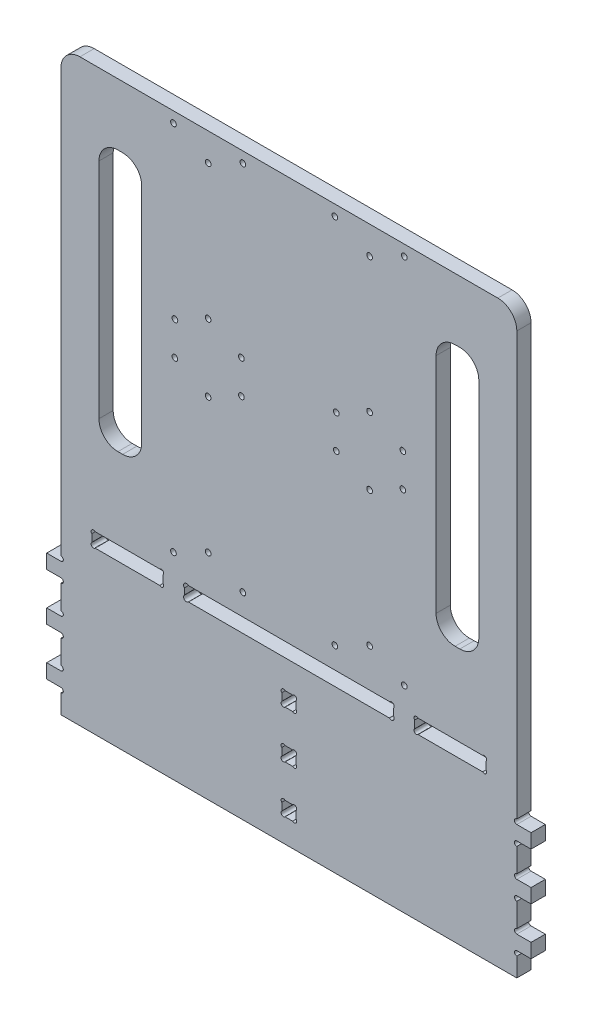
SolidWorks part; units mm, degrees
material "Balsa"
ref_plane "Front Plane" through (0, 0, 0) normal (0, 0, 1) x (1, 0, 0)
ref_plane "Top Plane" through (0, 0, 0) normal (0, 1, 0) x (1, 0, 0)
ref_plane "Right Plane" through (0, 0, 0) normal (1, 0, 0) x (0, 0, -1)
sketch "Sketch1" plane through (0, 0, 0) normal (0, 0, 1) x (1, 0, 0)
  line L0 (0, 222.25) -> (0, 0) construction
  line L1 (-304.8, 0) -> (304.8, 0)
  line L2 (-304.8, 0) -> (-304.8, 222.25)
  line L3 (-304.8, 222.25) -> (304.8, 222.25)
  line L4 (304.8, 0) -> (304.8, 222.25)
  line L5 (-304.8, 222.25) -> (-304.8, 184.15) construction
  line L6 (-304.8, 184.15) -> (-323.85, 184.15)
  line L7 (-304.8, 184.15) -> (-304.8, 165.1)
  line L8 (-304.8, 165.1) -> (-323.85, 165.1)
  line L9 (-323.85, 184.15) -> (-323.85, 165.1)
  line L10 (-304.8, 57.15) -> (-323.85, 57.15)
  line L11 (-304.8, 57.15) -> (-304.8, 38.1)
  line L12 (-304.8, 38.1) -> (-323.85, 38.1)
  line L13 (-323.85, 57.15) -> (-323.85, 38.1)
  line L14 (-304.8, 120.65) -> (-323.85, 120.65)
  line L15 (-304.8, 120.65) -> (-304.8, 101.6)
  line L16 (-304.8, 101.6) -> (-323.85, 101.6)
  line L17 (-323.85, 120.65) -> (-323.85, 101.6)
  line L18 (-323.85, 184.15) -> (-323.85, 222.25) construction
  line L19 (-323.85, 0) -> (-323.85, 38.1) construction
  line L20 (323.85, 0) -> (323.85, 38.1) construction
  line L21 (323.85, 184.15) -> (323.85, 222.25) construction
  line L22 (323.85, 120.65) -> (323.85, 101.6)
  line L23 (304.8, 101.6) -> (323.85, 101.6)
  line L24 (304.8, 120.65) -> (304.8, 101.6)
  line L25 (304.8, 120.65) -> (323.85, 120.65)
  line L26 (323.85, 57.15) -> (323.85, 38.1)
  line L27 (304.8, 38.1) -> (323.85, 38.1)
  line L28 (304.8, 57.15) -> (304.8, 38.1)
  line L29 (304.8, 57.15) -> (323.85, 57.15)
  line L30 (323.85, 184.15) -> (323.85, 165.1)
  line L31 (304.8, 165.1) -> (323.85, 165.1)
  line L32 (304.8, 184.15) -> (304.8, 165.1)
  line L33 (304.8, 184.15) -> (323.85, 184.15)
  line L34 (9.525, 38.1) -> (9.525, 0) construction
  line L35 (-9.525, 184.15) -> (9.525, 184.15) construction
  line L36 (-9.525, 184.15) -> (-9.525, 165.1) construction
  line L37 (-9.525, 165.1) -> (9.525, 165.1) construction
  line L38 (9.525, 184.15) -> (9.525, 165.1) construction
  line L39 (-9.525, 184.15) -> (9.525, 165.1) construction
  line L40 (-9.525, 165.1) -> (9.525, 184.15) construction
  line L41 (-9.525, 120.65) -> (9.525, 120.65) construction
  line L42 (-9.525, 120.65) -> (-9.525, 101.6) construction
  line L43 (-9.525, 101.6) -> (9.525, 101.6) construction
  line L44 (9.525, 120.65) -> (9.525, 101.6) construction
  line L45 (-9.525, 120.65) -> (9.525, 101.6) construction
  line L46 (-9.525, 101.6) -> (9.525, 120.65) construction
  line L47 (-9.525, 57.15) -> (9.525, 57.15) construction
  line L48 (-9.525, 57.15) -> (-9.525, 38.1) construction
  line L49 (-9.525, 38.1) -> (9.525, 38.1) construction
  line L50 (9.525, 57.15) -> (9.525, 38.1) construction
  line L51 (-9.525, 57.15) -> (9.525, 38.1) construction
  line L52 (-9.525, 38.1) -> (9.525, 57.15) construction
  line L53 (9.525, 184.15) -> (9.525, 222.25) construction
  line L54 (304.8, 781.05) -> (139.7, 781.05)
  line L55 (-304.8, 222.25) -> (-139.7, 222.25)
  line L56 (-304.8, 222.25) -> (-304.8, 781.05)
  line L57 (-304.8, 781.05) -> (-139.7, 781.05)
  line L58 (-139.7, 222.25) -> (-139.7, 781.05)
  line L59 (139.7, 222.25) -> (139.7, 781.05)
  line L60 (304.8, 222.25) -> (139.7, 222.25)
  line L61 (304.8, 222.25) -> (304.8, 781.05)
  line L62 (5.0349, 241.3) -> (-5.0349, 241.3)
  line L63 (-304.8, 781.05) -> (304.8, 781.05)
  line L64 (-304.8, 781.05) -> (-304.8, 241.3)
  line L65 (-304.8, 241.3) -> (304.8, 241.3)
  line L66 (304.8, 781.05) -> (304.8, 241.3)
  line L67 (-9.525, 236.8099) -> (-9.525, 226.7401)
  line L68 (-5.0349, 222.25) -> (5.0349, 222.25)
  line L69 (9.525, 226.7401) -> (9.525, 236.8099)
  line L70 (-9.525, 226.7401) -> (-9.525, 222.25) construction
  line L71 (-9.525, 222.25) -> (-5.0349, 222.25) construction
  line L72 (5.0349, 222.25) -> (9.525, 222.25) construction
  line L73 (9.525, 222.25) -> (9.525, 226.7401) construction
  line L74 (9.525, 236.8099) -> (9.525, 241.3) construction
  line L75 (9.525, 241.3) -> (5.0349, 241.3) construction
  line L76 (-5.0349, 241.3) -> (-9.525, 241.3) construction
  line L77 (-9.525, 241.3) -> (-9.525, 236.8099) construction
  line L78 (182.8349, 241.3) -> (172.7651, 241.3)
  line L79 (168.275, 236.8099) -> (168.275, 226.7401)
  line L80 (172.7651, 222.25) -> (182.8349, 222.25)
  line L81 (187.325, 226.7401) -> (187.325, 236.8099)
  line L82 (5.0349, 241.3) -> (182.8349, 241.3) construction
  line L83 (259.0349, 241.3) -> (248.9651, 241.3)
  line L84 (244.475, 236.8099) -> (244.475, 226.7401)
  line L85 (248.9651, 222.25) -> (259.0349, 222.25)
  line L86 (263.525, 226.7401) -> (263.525, 236.8099)
  line L87 (182.8349, 241.3) -> (259.0349, 241.3) construction
  line L88 (-263.525, 226.7401) -> (-263.525, 236.8099)
  line L89 (-248.9651, 222.25) -> (-259.0349, 222.25)
  line L90 (-244.475, 236.8099) -> (-244.475, 226.7401)
  line L91 (-259.0349, 241.3) -> (-248.9651, 241.3)
  line L92 (-187.325, 226.7401) -> (-187.325, 236.8099)
  line L93 (-172.7651, 222.25) -> (-182.8349, 222.25)
  line L94 (-168.275, 236.8099) -> (-168.275, 226.7401)
  line L95 (-182.8349, 241.3) -> (-172.7651, 241.3)
  line L96 (-139.7, 231.775) -> (139.7, 231.775) construction
  line L97 (-9.525, 241.3) -> (-9.525, 222.25)
  line L98 (9.525, 241.3) -> (9.525, 222.25)
  line L99 (0, -55) -> (0, 55) construction
  line L100 (-304.8, 730.25) -> (-381, 730.25)
  line L101 (-304.8, 730.25) -> (-304.8, 317.5)
  line L102 (-304.8, 317.5) -> (-381, 317.5)
  line L103 (-381, 730.25) -> (-381, 317.5)
  line L104 (-304.8, 704.85) -> (-355.6, 704.85)
  line L105 (-304.8, 704.85) -> (-304.8, 342.9)
  line L106 (-304.8, 342.9) -> (-355.6, 342.9)
  line L107 (-355.6, 704.85) -> (-355.6, 342.9)
  line L108 (304.8, 317.5) -> (381, 317.5)
  line L109 (381, 730.25) -> (381, 317.5)
  line L110 (304.8, 730.25) -> (381, 730.25)
  line L111 (304.8, 730.25) -> (304.8, 317.5)
  line L112 (304.8, 342.9) -> (355.6, 342.9)
  line L113 (355.6, 704.85) -> (355.6, 342.9)
  line L114 (304.8, 704.85) -> (355.6, 704.85)
  line L115 (304.8, 704.85) -> (304.8, 342.9)
  arc A0 (-5.0349, 241.3) -> (-9.525, 236.8099) centre (-7.2799, 239.0549) ccw
  arc A1 (-9.525, 226.7401) -> (-5.0349, 222.25) centre (-7.2799, 224.4951) ccw
  arc A2 (5.0349, 222.25) -> (9.525, 226.7401) centre (7.2799, 224.4951) ccw
  arc A3 (9.525, 236.8099) -> (5.0349, 241.3) centre (7.2799, 239.0549) ccw
  arc A4 (172.7651, 241.3) -> (168.275, 236.8099) centre (170.5201, 239.0549) ccw
  arc A5 (168.275, 226.7401) -> (172.7651, 222.25) centre (170.5201, 224.4951) ccw
  arc A6 (182.8349, 222.25) -> (187.325, 226.7401) centre (185.0799, 224.4951) ccw
  arc A7 (187.325, 236.8099) -> (182.8349, 241.3) centre (185.0799, 239.0549) ccw
  arc A8 (248.9651, 241.3) -> (244.475, 236.8099) centre (246.7201, 239.0549) ccw
  arc A9 (244.475, 226.7401) -> (248.9651, 222.25) centre (246.7201, 224.4951) ccw
  arc A10 (259.0349, 222.25) -> (263.525, 226.7401) centre (261.2799, 224.4951) ccw
  arc A11 (263.525, 236.8099) -> (259.0349, 241.3) centre (261.2799, 239.0549) ccw
  arc A12 (-263.525, 236.8099) -> (-259.0349, 241.3) centre (-261.2799, 239.0549) cw
  arc A13 (-259.0349, 222.25) -> (-263.525, 226.7401) centre (-261.2799, 224.4951) cw
  arc A14 (-244.475, 226.7401) -> (-248.9651, 222.25) centre (-246.7201, 224.4951) cw
  arc A15 (-248.9651, 241.3) -> (-244.475, 236.8099) centre (-246.7201, 239.0549) cw
  arc A16 (-187.325, 236.8099) -> (-182.8349, 241.3) centre (-185.0799, 239.0549) cw
  arc A17 (-182.8349, 222.25) -> (-187.325, 226.7401) centre (-185.0799, 224.4951) cw
  arc A18 (-168.275, 226.7401) -> (-172.7651, 222.25) centre (-170.5201, 224.4951) cw
  arc A19 (-172.7651, 241.3) -> (-168.275, 236.8099) centre (-170.5201, 239.0549) cw
  circle A20 centre (-136.9984, 224.9516) radius 3.8207
  circle A21 centre (-136.9984, 238.5984) radius 3.8207
  circle A22 centre (136.9984, 224.9516) radius 3.8207
  circle A23 centre (136.9984, 238.5984) radius 3.8207
  point P20 (-304.8, 111.125)
  point P21 (-304.8, 111.125)
  point P37 (0, 174.625)
  point P42 (0, 111.125)
  point P47 (0, 47.625)
  point P132 (-139.7, 227.6532)
  point P133 (-134.2968, 222.25)
  point P150 (-342.9, 730.25)
  line B0 (9.525, 169.5901) -> (9.525, 179.6599)
  line B1 (-5.0349, 165.1) -> (5.0349, 165.1)
  line B2 (-9.525, 179.6599) -> (-9.525, 169.5901)
  line B3 (5.0349, 184.15) -> (-5.0349, 184.15)
  arc B4 (5.0349, 165.1) -> (9.525, 169.5901) centre (7.2799, 167.3451) ccw
  arc B5 (-9.525, 169.5901) -> (-5.0349, 165.1) centre (-7.2799, 167.3451) ccw
  arc B6 (-5.0349, 184.15) -> (-9.525, 179.6599) centre (-7.2799, 181.9049) ccw
  arc B7 (9.525, 179.6599) -> (5.0349, 184.15) centre (7.2799, 181.9049) ccw
  line B8 (9.525, 106.0901) -> (9.525, 116.1599)
  line B9 (-5.0349, 101.6) -> (5.0349, 101.6)
  line B10 (-9.525, 116.1599) -> (-9.525, 106.0901)
  line B11 (5.0349, 120.65) -> (-5.0349, 120.65)
  arc B12 (5.0349, 101.6) -> (9.525, 106.0901) centre (7.2799, 103.8451) ccw
  arc B13 (-9.525, 106.0901) -> (-5.0349, 101.6) centre (-7.2799, 103.8451) ccw
  arc B14 (-5.0349, 120.65) -> (-9.525, 116.1599) centre (-7.2799, 118.4049) ccw
  arc B15 (9.525, 116.1599) -> (5.0349, 120.65) centre (7.2799, 118.4049) ccw
  line B16 (9.525, 42.5901) -> (9.525, 52.6599)
  line B17 (-5.0349, 38.1) -> (5.0349, 38.1)
  line B18 (-9.525, 52.6599) -> (-9.525, 42.5901)
  line B19 (5.0349, 57.15) -> (-5.0349, 57.15)
  arc B20 (5.0349, 38.1) -> (9.525, 42.5901) centre (7.2799, 40.3451) ccw
  arc B21 (-9.525, 42.5901) -> (-5.0349, 38.1) centre (-7.2799, 40.3451) ccw
  arc B22 (-5.0349, 57.15) -> (-9.525, 52.6599) centre (-7.2799, 54.9049) ccw
  arc B23 (9.525, 52.6599) -> (5.0349, 57.15) centre (7.2799, 54.9049) ccw
  dimension "D12" = 3.175
  dimension "D17" = 5.4032
  dimension "D1" = 609.6
  dimension "D2" = 222.25
  dimension "D3" = 19.05
  dimension "D4" = 38.1
  dimension "D5" = 19.05
  dimension "D6" = 38.1
  dimension "D7" = 44.45
  dimension "D8" = 558.8
  dimension "D9" = 165.1
  dimension "D10" = 19.05
  dimension "D11" = 295.275
  dimension "D14" = 177.8
  dimension "D16" = 76.2
  dimension "D18" = 5.4032
  dimension "D19" = 9.525
  dimension "D20" = 50.8
  dimension "D21" = 25.4
  dimension "D22" = 76.2
  dimension "D23" = 25.4
  dimension "D24" = 25.4
  dimension "D25" = 76.2
  dimension "D13" = 2
  dimension "D15" = 2
sketch_block_instance "NotchCutoutProfile-5"
sketch_block "NotchCutoutProfile"
sketch_block_instance "NotchCutoutProfile-6"
sketch_block_instance "NotchCutoutProfile-8"
extrude "Boss-Extrude1" add sketch "Sketch1" against normal blind 19.05 contours L6 L9 L8 L2 | L1 L4 L3 L2 L35 L38 L37 L36 L41 L44 L43 L42 L47 L50 L49 L48 | L14 L17 L16 L2 | L10 L13 L12 L2 | L33 L4 L31 L30 | L25 L4 L23 L22 | L29 L4 L27 L26 | L3 L58 L57 L56 | L3 L61 L54 L59 | L65 L56 L3 L58 | L65 L59 L3 L61 | L58 L65 L59 L63 | L3 A13 L88 A12 L65 L56 | L65 A19 L94 A18 L55 L58 | A5 L79 A4 L65 L59 L3 | A11 L86 A10 L60 L61 L65 | L3 A1 | L3 A2 | L65 A3 | L65 A0 | L114 L111 L112 L113 | L104 L107 L106 L101
sketch "Sketch2" plane through (0, 0, 0) normal (0, 0, 1) x (1, 0, 0)
  line L0 (304.8, 0) -> (304.8, 38.1) construction
  line L5 (-304.8, 0) -> (304.8, 0)
  line L6 (-304.8, 0) -> (-304.8, 6.35)
  line L7 (-304.8, 6.35) -> (304.8, 6.35)
  line L8 (304.8, 0) -> (304.8, 6.35)
  dimension "D1" = 6.35
extrude "Cut-Extrude1" cut sketch "Sketch2" against normal through all both and the other way through all
sketch "Sketch3" plane through (-323.85, 0, 0) normal (-1, 0, 0) x (0, 0, 1)
  line B0 (0, 38.1) -> (0, 57.15)
  line B1 (0, 57.15) -> (-19.05, 57.15)
  line B2 (-19.05, 57.15) -> (-19.05, 38.1)
  line B3 (-19.05, 38.1) -> (0, 38.1)
  line B4 (0, 101.6) -> (0, 120.65)
  line B5 (0, 120.65) -> (-19.05, 120.65)
  line B6 (-19.05, 120.65) -> (-19.05, 101.6)
  line B7 (-19.05, 101.6) -> (0, 101.6)
  line B8 (0, 165.1) -> (0, 184.15)
  line B9 (0, 184.15) -> (-19.05, 184.15)
  line B10 (-19.05, 184.15) -> (-19.05, 165.1)
  line B11 (-19.05, 165.1) -> (0, 165.1)
sketch_block_instance "Block1-1"
sketch_block "Block1"
sketch "Sketch4" plane through (0, 0, 0) normal (0, 0, 1) x (1, 0, 0)
  line L0 (-304.8, 165.1) -> (-323.85, 165.1) construction
  line L1 (-323.85, 184.15) -> (-323.85, 165.1) construction
  line L30 (-304.8, 6.35) -> (304.8, 6.35)
  line L31 (304.8, 6.35) -> (304.8, 38.1)
  line L32 (304.8, 38.1) -> (323.85, 38.1)
  line L33 (323.85, 38.1) -> (323.85, 57.15)
  line L34 (323.85, 57.15) -> (304.8, 57.15)
  line L35 (304.8, 57.15) -> (304.8, 101.6)
  line L36 (304.8, 101.6) -> (323.85, 101.6)
  line L37 (323.85, 101.6) -> (323.85, 120.65)
  line L38 (323.85, 120.65) -> (304.8, 120.65)
  line L39 (304.8, 120.65) -> (304.8, 165.1)
  line L40 (304.8, 165.1) -> (323.85, 165.1)
  line L41 (323.85, 165.1) -> (323.85, 184.15)
  line L42 (323.85, 184.15) -> (304.8, 184.15)
  line L43 (304.8, 184.15) -> (304.8, 317.5)
  line L44 (304.8, 781.05) -> (-304.8, 781.05)
  line L45 (-304.8, 317.5) -> (-304.8, 184.15)
  line L46 (-304.8, 184.15) -> (-323.85, 184.15)
  line L47 (-323.85, 184.15) -> (-323.85, 165.1)
  line L48 (-323.85, 165.1) -> (-304.8, 165.1)
  line L49 (-304.8, 165.1) -> (-304.8, 120.65)
  line L50 (-304.8, 120.65) -> (-323.85, 120.65)
  line L51 (-323.85, 120.65) -> (-323.85, 101.6)
  line L52 (-323.85, 101.6) -> (-304.8, 101.6)
  line L53 (-304.8, 101.6) -> (-304.8, 57.15)
  line L54 (-304.8, 57.15) -> (-323.85, 57.15)
  line L55 (-323.85, 57.15) -> (-323.85, 38.1)
  line L56 (-323.85, 38.1) -> (-304.8, 38.1)
  line L57 (-304.8, 38.1) -> (-304.8, 6.35)
  line L58 (-304.8, 6.35) -> (304.8, 6.35)
  line L59 (304.8, 6.35) -> (304.8, 38.1)
  line L60 (304.8, 38.1) -> (323.85, 38.1)
  line L61 (323.85, 38.1) -> (323.85, 57.15)
  line L62 (323.85, 57.15) -> (304.8, 57.15)
  line L63 (304.8, 57.15) -> (304.8, 101.6)
  line L64 (304.8, 101.6) -> (323.85, 101.6)
  line L65 (323.85, 101.6) -> (323.85, 120.65)
  line L66 (323.85, 120.65) -> (304.8, 120.65)
  line L67 (304.8, 120.65) -> (304.8, 165.1)
  line L68 (304.8, 165.1) -> (323.85, 165.1)
  line L69 (323.85, 165.1) -> (323.85, 184.15)
  line L70 (323.85, 184.15) -> (304.8, 184.15)
  line L71 (304.8, 184.15) -> (304.8, 317.5)
  line L73 (-304.8, 317.5) -> (-304.8, 184.15)
  line L74 (-304.8, 184.15) -> (-323.85, 184.15)
  line L75 (-323.85, 184.15) -> (-323.85, 165.1)
  line L76 (-323.85, 165.1) -> (-304.8, 165.1)
  line L77 (-304.8, 165.1) -> (-304.8, 120.65)
  line L78 (-304.8, 120.65) -> (-323.85, 120.65)
  line L79 (-323.85, 120.65) -> (-323.85, 101.6)
  line L80 (-323.85, 101.6) -> (-304.8, 101.6)
  line L81 (-304.8, 101.6) -> (-304.8, 57.15)
  line L82 (-304.8, 57.15) -> (-323.85, 57.15)
  line L83 (-323.85, 57.15) -> (-323.85, 38.1)
  line L84 (-323.85, 38.1) -> (-304.8, 38.1)
  line L85 (-304.8, 38.1) -> (-304.8, 6.35)
  line L86 (304.8, 781.05) -> (-304.8, 781.05)
  line L95 (304.8, 730.25) -> (304.8, 781.05)
  line L96 (304.8, 730.25) -> (304.8, 781.05)
  line L97 (-304.8, 781.05) -> (-304.8, 730.25)
  line L98 (-304.8, 781.05) -> (-304.8, 730.25)
  line L99 (304.8, 317.5) -> (381, 317.5)
  line L100 (304.8, 317.5) -> (381, 317.5)
  line L101 (381, 317.5) -> (381, 730.25)
  line L102 (381, 317.5) -> (381, 730.25)
  line L103 (381, 730.25) -> (304.8, 730.25)
  line L104 (381, 730.25) -> (304.8, 730.25)
  line L105 (-304.8, 730.25) -> (-381, 730.25)
  line L106 (-304.8, 730.25) -> (-381, 730.25)
  line L107 (-381, 730.25) -> (-381, 317.5)
  line L108 (-381, 730.25) -> (-381, 317.5)
  line L109 (-381, 317.5) -> (-304.8, 317.5)
  line L110 (-381, 317.5) -> (-304.8, 317.5)
  line B0 (-304.8, 165.1) -> (-323.85, 165.1)
  line B1 (-323.85, 165.1) -> (-323.85, 184.15)
  line B2 (-323.85, 184.15) -> (-304.8, 184.15)
  arc B3 (-304.8, 165.1) -> (-304.8, 158.75) centre (-304.8, 161.925) cw
  arc B4 (-304.8, 184.15) -> (-304.8, 190.5) centre (-304.8, 187.325) ccw
  line B5 (-304.8, 101.6) -> (-323.85, 101.6)
  line B6 (-323.85, 101.6) -> (-323.85, 120.65)
  line B7 (-323.85, 120.65) -> (-304.8, 120.65)
  arc B8 (-304.8, 101.6) -> (-304.8, 95.25) centre (-304.8, 98.425) cw
  arc B9 (-304.8, 120.65) -> (-304.8, 127) centre (-304.8, 123.825) ccw
  line B10 (-304.8, 38.1) -> (-323.85, 38.1)
  line B11 (-323.85, 38.1) -> (-323.85, 57.15)
  line B12 (-323.85, 57.15) -> (-304.8, 57.15)
  arc B13 (-304.8, 38.1) -> (-304.8, 31.75) centre (-304.8, 34.925) cw
  arc B14 (-304.8, 57.15) -> (-304.8, 63.5) centre (-304.8, 60.325) ccw
  line B15 (304.8, 184.15) -> (323.85, 184.15)
  line B16 (323.85, 184.15) -> (323.85, 165.1)
  line B17 (323.85, 165.1) -> (304.8, 165.1)
  arc B18 (304.8, 184.15) -> (304.8, 190.5) centre (304.8, 187.325) cw
  arc B19 (304.8, 165.1) -> (304.8, 158.75) centre (304.8, 161.925) ccw
  line B20 (304.8, 120.65) -> (323.85, 120.65)
  line B21 (323.85, 120.65) -> (323.85, 101.6)
  line B22 (323.85, 101.6) -> (304.8, 101.6)
  arc B23 (304.8, 120.65) -> (304.8, 127) centre (304.8, 123.825) cw
  arc B24 (304.8, 101.6) -> (304.8, 95.25) centre (304.8, 98.425) ccw
  line B25 (304.8, 57.15) -> (323.85, 57.15)
  line B26 (323.85, 57.15) -> (323.85, 38.1)
  line B27 (323.85, 38.1) -> (304.8, 38.1)
  arc B28 (304.8, 57.15) -> (304.8, 63.5) centre (304.8, 60.325) cw
  arc B29 (304.8, 38.1) -> (304.8, 31.75) centre (304.8, 34.925) ccw
  dimension "D1" = 0
sketch_block_instance "DogBoneCornerNotch-1"
sketch_block "DogBoneCornerNotch" parameters "D1"=19.05, "D2"=19.05, "D3"=19.05
sketch_block_instance "DogBoneCornerNotch-2"
sketch_block_instance "DogBoneCornerNotch-3"
sketch_block_instance "DogBoneCornerNotch-4"
sketch_block_instance "DogBoneCornerNotch-5"
sketch_block_instance "DogBoneCornerNotch-6"
extrude "Cut-Extrude2" cut sketch "Sketch4" against normal through all contours L73 B4 | B3 L77 | L77 B9 | B8 L81 | B13 L85 | L81 B14 | L59 B29 | B28 L63 | L63 B24 | B23 L67 | L67 B19 | B18 L71
sketch "Sketch5" plane through (0, 0, 0) normal (0, 0, 1) x (1, 0, 0)
  line L0 (-134.2968, 241.3) -> (134.2968, 241.3) construction
  line L5 (-304.8, 190.5) -> (-304.8, 317.5) construction
  line L10 (-15.1138, 247.65) -> (-200.7862, 247.65) construction
  line L11 (-15.1138, 788.9676) -> (-246.4147, 788.9676) construction
  line L12 (-15.1138, 788.9676) -> (-15.1138, 247.65) construction
  line L13 (-15.1138, 518.3088) -> (-243.6618, 518.3088) construction
  line L14 (-107.95, 247.65) -> (-107.95, 518.3088) construction
  line L15 (-107.95, 518.3088) -> (-107.95, 788.9676) construction
  line L16 (-200.7862, 247.65) -> (-215.6571, 673.4971) construction
  line L17 (-107.95, 292.8094) -> (-107.95, 247.65) construction
  line L18 (-107.95, 247.65) -> (-107.95, 269.9494) construction
  line L19 (-107.95, 269.9494) -> (-15.1138, 269.9494) construction
  line L20 (0, -10.4775) -> (0, 10.4775) construction
  line L21 (107.95, 269.9494) -> (15.1138, 269.9494) construction
  line L22 (107.95, 247.65) -> (107.95, 269.9494) construction
  line L23 (107.95, 292.8094) -> (107.95, 247.65) construction
  line L24 (200.7862, 247.65) -> (215.6571, 673.4971) construction
  line L25 (107.95, 518.3088) -> (107.95, 788.9676) construction
  line L26 (107.95, 247.65) -> (107.95, 518.3088) construction
  line L27 (15.1138, 518.3088) -> (243.6618, 518.3088) construction
  line L28 (15.1138, 788.9676) -> (15.1138, 247.65) construction
  line L29 (15.1138, 788.9676) -> (246.4147, 788.9676) construction
  line L30 (15.1138, 247.65) -> (200.7862, 247.65) construction
  circle A4 centre (-107.95, 743.8082) radius 3.81
  circle A5 centre (-107.95, 563.4682) radius 3.81
  circle A6 centre (-107.95, 473.1494) radius 3.81
  circle A7 centre (-107.95, 292.8094) radius 3.81
  circle A8 centre (-61.5319, 269.9494) radius 3.81
  circle A9 centre (-63.5, 540.6082) radius 3.81
  circle A10 centre (-61.5319, 766.6682) radius 3.81
  circle A11 centre (-63.5, 496.0094) radius 3.81
  circle A12 centre (-154.3681, 269.9494) radius 3.81
  circle A13 centre (-152.4, 540.6082) radius 3.81
  circle A14 centre (-152.4, 496.0094) radius 3.81
  circle A15 centre (-154.3681, 766.6682) radius 3.81
  circle A16 centre (154.3681, 766.6682) radius 3.81
  circle A17 centre (152.4, 496.0094) radius 3.81
  circle A18 centre (152.4, 540.6082) radius 3.81
  circle A19 centre (154.3681, 269.9494) radius 3.81
  circle A20 centre (63.5, 496.0094) radius 3.81
  circle A21 centre (61.5319, 766.6682) radius 3.81
  circle A22 centre (63.5, 540.6082) radius 3.81
  circle A23 centre (61.5319, 269.9494) radius 3.81
  circle A24 centre (107.95, 292.8094) radius 3.81
  circle A25 centre (107.95, 473.1494) radius 3.81
  circle A26 centre (107.95, 563.4682) radius 3.81
  circle A27 centre (107.95, 743.8082) radius 3.81
  point P10 (-107.95, 653.6382)
  point P18 (-107.95, 382.9794)
  dimension "D5" = 90.17
  dimension "D1" = 7.62
  dimension "D2" = 7.62
  dimension "D6" = 7.62
  dimension "D10" = 7.62
  dimension "D11" = 7.62
  dimension "D14" = 22.86
  dimension "D15" = 92.8362
  dimension "D3" = 90.17
  dimension "D4" = 90.17
  dimension "D7" = 90.17
  dimension "D8" = 541.3176
  dimension "D9" = 22.86
  dimension "D12" = 6.35
  dimension "D13" = 2
  dimension "D16" = 127
  dimension "D17" = 88.9
extrude "Cut-Extrude3" cut sketch "Sketch5" against normal up to surface (19.05 mm away) up to face at (0, 174.625, -19.05)
sketch "Sketch7" plane through (0, 0, 0) normal (0, 0, 1) x (1, 0, 0)
  line L0 (-304.8, 317.5) -> (-381, 317.5) construction
  line L1 (-254, 698.5) -> (-196.85, 698.5)
  line L2 (-254, 698.5) -> (-254, 349.25)
  line L3 (-254, 349.25) -> (-196.85, 349.25)
  line L4 (-196.85, 698.5) -> (-196.85, 349.25)
  line L5 (-381, 730.25) -> (-381, 317.5) construction
  line L7 (-304.8, 730.25) -> (-381, 730.25) construction
  dimension "D1" = 31.75
  dimension "D2" = 127
  dimension "D3" = 57.15
  dimension "D4" = 31.75
extrude "Cut-Extrude5" cut sketch "Sketch7" against normal through all
mirror "Mirror1" about plane through (0, 0, 0) normal (1, 0, 0) of "Cut-Extrude5"
fillet "Fillet3" radius 25.4 18 edges at (-304.8, 781.05, -9.525) (304.8, 781.05, -9.525) (304.8, 317.5, -9.525) (304.8, 730.25, -9.525) (-304.8, 730.25, -9.525) (-304.8, 317.5, -9.525) (-381, 317.5, -9.525) (-381, 730.25, -9.525) (381, 730.25, -9.525) (381, 317.5, -9.525) (-254, 349.25, -9.525) (-254, 698.5, -9.525) (-196.85, 698.5, -9.525) (-196.85, 349.25, -9.525) (254, 698.5, -9.525) (254, 349.25, -9.525) (196.85, 349.25, -9.525) (196.85, 698.5, -9.525)
sketch "Sketch8" plane through (0, 0, 0) normal (0, 0, 1) x (1, 0, 0)
  line L0 (-254, 673.1) -> (-254, 374.65) construction
  line L1 (-254, 539.75) -> (-196.85, 539.75)
  line L2 (-254, 539.75) -> (-254, 508)
  line L3 (-254, 508) -> (-196.85, 508)
  line L4 (-196.85, 539.75) -> (-196.85, 508)
  line L5 (-196.85, 374.65) -> (-196.85, 673.1) construction
  line L6 (-222.25, 698.5) -> (-228.6, 698.5) construction
  line L7 (-228.6, 349.25) -> (-222.25, 349.25) construction
  point P10 (-225.425, 698.5)
  dimension "D1" = 158.75
  dimension "D2" = 158.75
extrude "Boss-Extrude2" add sketch "Sketch8" against normal up to surface (19.05 mm away) up to face at (0, 249.4254, -19.05)
sketch "Sketch11" plane through (0, 0, 0) normal (0, 0, 1) x (1, 0, 0)
  line L0 (-254, 539.75) -> (-254, 508)
  line L1 (-254, 508) -> (-196.85, 508)
  line L2 (-196.85, 508) -> (-196.85, 539.75)
  line L3 (-196.85, 539.75) -> (-254, 539.75)
  line L14 (-304.8, 755.65) -> (-304.8, 292.1)
  line L15 (-304.8, 292.1) -> (-406.39, 292.1)
  line L16 (-406.39, 292.1) -> (-406.39, 755.65)
  line L17 (-406.39, 755.65) -> (-304.8, 755.65)
  line L18 (406.39, 755.65) -> (304.8, 755.65)
  line L19 (406.39, 292.1) -> (406.39, 755.65)
  line L20 (304.8, 292.1) -> (406.39, 292.1)
  line L21 (304.8, 755.65) -> (304.8, 292.1)
extrude "Cut-Extrude7" cut sketch "Sketch11" against normal blind 211.328
mirror "Mirror2" about plane through (0, 0, 0) normal (1, 0, 0) of "Boss-Extrude2"
sketch "Sketch9" plane through (0, 0, -19.05) normal (0, 0, -1) x (-1, 0, 0)
  line L0 (-248.9651, 222.25) -> (-259.0349, 222.25) construction
  line L1 (-263.525, 226.7401) -> (-263.525, 236.8099) construction
  line L2 (-248.9651, 241.3) -> (-259.0349, 241.3) construction
  line L3 (-168.275, 236.8099) -> (-168.275, 226.7401) construction
  line L4 (-248.9651, 222.25) -> (-259.0349, 222.25)
  line L5 (-263.525, 226.7401) -> (-263.525, 236.8099)
  line L6 (-248.9651, 241.3) -> (-259.0349, 241.3)
  line L7 (-168.275, 236.8099) -> (-168.275, 226.7401)
  line L8 (-248.9651, 241.3) -> (-172.7651, 241.3)
  line L9 (-172.7651, 222.25) -> (-248.9651, 222.25)
  line L10 (0, 0) -> (0, 781.05) construction
  line L11 (9.525, 0) -> (-9.525, 0) construction
  line L12 (-279.4, 781.05) -> (279.4, 781.05) construction
  line L13 (168.275, 236.8099) -> (168.275, 226.7401)
  line L14 (248.9651, 241.3) -> (172.7651, 241.3)
  line L15 (248.9651, 241.3) -> (259.0349, 241.3)
  line L16 (263.525, 226.7401) -> (263.525, 236.8099)
  line L17 (248.9651, 222.25) -> (259.0349, 222.25)
  line L18 (172.7651, 222.25) -> (248.9651, 222.25)
  arc A0 (-168.275, 236.8099) -> (-172.7651, 241.3) centre (-170.5201, 239.0549) ccw construction
  arc A1 (-172.7651, 222.25) -> (-168.275, 226.7401) centre (-170.5201, 224.4951) ccw construction
  arc A2 (-263.525, 226.7401) -> (-259.0349, 222.25) centre (-261.2799, 224.4951) ccw construction
  arc A3 (-259.0349, 241.3) -> (-263.525, 236.8099) centre (-261.2799, 239.0549) ccw construction
  arc A4 (-168.275, 236.8099) -> (-172.7651, 241.3) centre (-170.5201, 239.0549) ccw
  arc A5 (-172.7651, 222.25) -> (-168.275, 226.7401) centre (-170.5201, 224.4951) ccw
  arc A6 (-263.525, 226.7401) -> (-259.0349, 222.25) centre (-261.2799, 224.4951) ccw
  arc A7 (-259.0349, 241.3) -> (-263.525, 236.8099) centre (-261.2799, 239.0549) ccw
  arc A8 (172.7651, 222.25) -> (168.275, 226.7401) centre (170.5201, 224.4951) cw
  arc A9 (168.275, 236.8099) -> (172.7651, 241.3) centre (170.5201, 239.0549) cw
  arc A10 (259.0349, 241.3) -> (263.525, 236.8099) centre (261.2799, 239.0549) cw
  arc A11 (263.525, 226.7401) -> (259.0349, 222.25) centre (261.2799, 224.4951) cw
extrude "Cut-Extrude6" cut sketch "Sketch9" against normal through all both and the other way through all
sketch "Sketch10" plane through (0, 0, -19.05) normal (0, 0, -1) x (-1, 0, 0)
  line L0 (-248.9651, 241.3) -> (-244.475, 241.3)
  line L1 (-187.325, 241.3) -> (-182.8349, 241.3)
  line L2 (-182.8349, 222.25) -> (-187.325, 222.25)
  line L3 (-244.475, 222.25) -> (-248.9651, 222.25)
  line L4 (0, 0) -> (0, 781.05) construction
  line L5 (-279.4, 781.05) -> (279.4, 781.05) construction
  line L6 (244.475, 222.25) -> (248.9651, 222.25)
  line L7 (182.8349, 222.25) -> (187.325, 222.25)
  line L8 (187.325, 241.3) -> (182.8349, 241.3)
  line L9 (248.9651, 241.3) -> (244.475, 241.3)
  arc A0 (-248.9651, 222.25) -> (-244.475, 222.25) centre (-246.7201, 224.4951) ccw construction
  arc A1 (-187.325, 222.25) -> (-182.8349, 222.25) centre (-185.0799, 224.4951) ccw construction
  arc A2 (-182.8349, 241.3) -> (-187.325, 241.3) centre (-185.0799, 239.0549) ccw construction
  arc A3 (-244.475, 241.3) -> (-248.9651, 241.3) centre (-246.7201, 239.0549) ccw construction
  arc A4 (-248.9651, 222.25) -> (-244.475, 222.25) centre (-246.7201, 224.4951) ccw
  arc A5 (-187.325, 222.25) -> (-182.8349, 222.25) centre (-185.0799, 224.4951) ccw
  arc A6 (-182.8349, 241.3) -> (-187.325, 241.3) centre (-185.0799, 239.0549) ccw
  arc A7 (-244.475, 241.3) -> (-248.9651, 241.3) centre (-246.7201, 239.0549) ccw
  arc A8 (244.475, 241.3) -> (248.9651, 241.3) centre (246.7201, 239.0549) cw
  arc A9 (182.8349, 241.3) -> (187.325, 241.3) centre (185.0799, 239.0549) cw
  arc A10 (187.325, 222.25) -> (182.8349, 222.25) centre (185.0799, 224.4951) cw
  arc A11 (248.9651, 222.25) -> (244.475, 222.25) centre (246.7201, 224.4951) cw
extrude "Boss-Extrude3" add sketch "Sketch10" against normal up to surface (19.05 mm away) up to face at (215.9, 231.775, 0)
sketch "Sketch12" plane through (0, 0, 0) normal (0, 0, 1) x (1, 0, 0)
  line L0 (196.85, 539.75) -> (196.85, 673.1) construction
  line L1 (196.85, 609.3243) -> (254, 609.3243)
  line L2 (196.85, 609.3243) -> (196.85, 497.074)
  line L3 (196.85, 497.074) -> (254, 497.074)
  line L4 (254, 609.3243) -> (254, 497.074)
  line L5 (254, 508) -> (254, 374.65) construction
extrude "Cut-Extrude8" cut sketch "Sketch12" against normal blind 228.346
sketch "Sketch14" plane through (0, 0, 0) normal (0, 0, 1) x (1, 0, 0)
  line L28 (304.8, 190.5) -> (304.8, 755.65)
  line L29 (279.4, 781.05) -> (-279.4, 781.05)
  line L30 (-304.8, 755.65) -> (-304.8, 190.5)
  line L31 (-304.8, 184.15) -> (-323.85, 184.15)
  line L32 (-323.85, 184.15) -> (-323.85, 165.1)
  line L33 (-323.85, 165.1) -> (-304.8, 165.1)
  line L34 (-304.8, 158.75) -> (-304.8, 127)
  line L35 (-304.8, 120.65) -> (-323.85, 120.65)
  line L36 (-323.85, 120.65) -> (-323.85, 101.6)
  line L37 (-323.85, 101.6) -> (-304.8, 101.6)
  line L38 (-304.8, 95.25) -> (-304.8, 63.5)
  line L39 (-304.8, 57.15) -> (-323.85, 57.15)
  line L40 (-323.85, 57.15) -> (-323.85, 38.1)
  line L41 (-323.85, 38.1) -> (-304.8, 38.1)
  line L42 (-304.8, 31.75) -> (-304.8, 6.35)
  line L43 (-304.8, 6.35) -> (304.8, 6.35)
  line L44 (304.8, 6.35) -> (304.8, 31.75)
  line L45 (304.8, 38.1) -> (323.85, 38.1)
  line L46 (323.85, 38.1) -> (323.85, 57.15)
  line L47 (323.85, 57.15) -> (304.8, 57.15)
  line L48 (304.8, 63.5) -> (304.8, 95.25)
  line L49 (304.8, 101.6) -> (323.85, 101.6)
  line L50 (323.85, 101.6) -> (323.85, 120.65)
  line L51 (323.85, 120.65) -> (304.8, 120.65)
  line L52 (304.8, 127) -> (304.8, 158.75)
  line L53 (304.8, 165.1) -> (323.85, 165.1)
  line L54 (323.85, 165.1) -> (323.85, 184.15)
  line L55 (323.85, 184.15) -> (304.8, 184.15)
  line L56 (304.8, 190.5) -> (304.8, 755.65)
  line L57 (279.4, 781.05) -> (-279.4, 781.05)
  line L58 (-304.8, 755.65) -> (-304.8, 190.5)
  line L59 (-304.8, 184.15) -> (-323.85, 184.15)
  line L60 (-323.85, 184.15) -> (-323.85, 165.1)
  line L61 (-323.85, 165.1) -> (-304.8, 165.1)
  line L62 (-304.8, 158.75) -> (-304.8, 127)
  line L63 (-304.8, 120.65) -> (-323.85, 120.65)
  line L64 (-323.85, 120.65) -> (-323.85, 101.6)
  line L65 (-323.85, 101.6) -> (-304.8, 101.6)
  line L66 (-304.8, 95.25) -> (-304.8, 63.5)
  line L67 (-304.8, 57.15) -> (-323.85, 57.15)
  line L68 (-323.85, 57.15) -> (-323.85, 38.1)
  line L69 (-323.85, 38.1) -> (-304.8, 38.1)
  line L70 (-304.8, 31.75) -> (-304.8, 6.35)
  line L71 (-304.8, 6.35) -> (304.8, 6.35)
  line L72 (304.8, 6.35) -> (304.8, 31.75)
  line L73 (304.8, 38.1) -> (323.85, 38.1)
  line L74 (323.85, 38.1) -> (323.85, 57.15)
  line L75 (323.85, 57.15) -> (304.8, 57.15)
  line L76 (304.8, 63.5) -> (304.8, 95.25)
  line L77 (304.8, 101.6) -> (323.85, 101.6)
  line L78 (323.85, 101.6) -> (323.85, 120.65)
  line L79 (323.85, 120.65) -> (304.8, 120.65)
  line L80 (304.8, 127) -> (304.8, 158.75)
  line L81 (304.8, 165.1) -> (323.85, 165.1)
  line L82 (323.85, 165.1) -> (323.85, 184.15)
  line L83 (323.85, 184.15) -> (304.8, 184.15)
  arc A14 (304.8, 755.65) -> (279.4, 781.05) centre (279.4, 755.65) ccw
  arc A15 (-279.4, 781.05) -> (-304.8, 755.65) centre (-279.4, 755.65) ccw
  arc A16 (-304.8, 184.15) -> (-304.8, 190.5) centre (-304.8, 187.325) ccw
  arc A17 (-304.8, 158.75) -> (-304.8, 165.1) centre (-304.8, 161.925) ccw
  arc A18 (-304.8, 120.65) -> (-304.8, 127) centre (-304.8, 123.825) ccw
  arc A19 (-304.8, 95.25) -> (-304.8, 101.6) centre (-304.8, 98.425) ccw
  arc A20 (-304.8, 57.15) -> (-304.8, 63.5) centre (-304.8, 60.325) ccw
  arc A21 (-304.8, 31.75) -> (-304.8, 38.1) centre (-304.8, 34.925) ccw
  arc A22 (304.8, 38.1) -> (304.8, 31.75) centre (304.8, 34.925) ccw
  arc A23 (304.8, 63.5) -> (304.8, 57.15) centre (304.8, 60.325) ccw
  arc A24 (304.8, 101.6) -> (304.8, 95.25) centre (304.8, 98.425) ccw
  arc A25 (304.8, 127) -> (304.8, 120.65) centre (304.8, 123.825) ccw
  arc A26 (304.8, 165.1) -> (304.8, 158.75) centre (304.8, 161.925) ccw
  arc A27 (304.8, 190.5) -> (304.8, 184.15) centre (304.8, 187.325) ccw
  arc A28 (304.8, 755.65) -> (279.4, 781.05) centre (279.4, 755.65) ccw
  arc A29 (-279.4, 781.05) -> (-304.8, 755.65) centre (-279.4, 755.65) ccw
  arc A30 (-304.8, 184.15) -> (-304.8, 190.5) centre (-304.8, 187.325) ccw
  arc A31 (-304.8, 158.75) -> (-304.8, 165.1) centre (-304.8, 161.925) ccw
  arc A32 (-304.8, 120.65) -> (-304.8, 127) centre (-304.8, 123.825) ccw
  arc A33 (-304.8, 95.25) -> (-304.8, 101.6) centre (-304.8, 98.425) ccw
  arc A34 (-304.8, 57.15) -> (-304.8, 63.5) centre (-304.8, 60.325) ccw
  arc A35 (-304.8, 31.75) -> (-304.8, 38.1) centre (-304.8, 34.925) ccw
  arc A36 (304.8, 38.1) -> (304.8, 31.75) centre (304.8, 34.925) ccw
  arc A37 (304.8, 63.5) -> (304.8, 57.15) centre (304.8, 60.325) ccw
  arc A38 (304.8, 101.6) -> (304.8, 95.25) centre (304.8, 98.425) ccw
  arc A39 (304.8, 127) -> (304.8, 120.65) centre (304.8, 123.825) ccw
  arc A40 (304.8, 165.1) -> (304.8, 158.75) centre (304.8, 161.925) ccw
  arc A41 (304.8, 190.5) -> (304.8, 184.15) centre (304.8, 187.325) ccw
  dimension "D1" = 0
